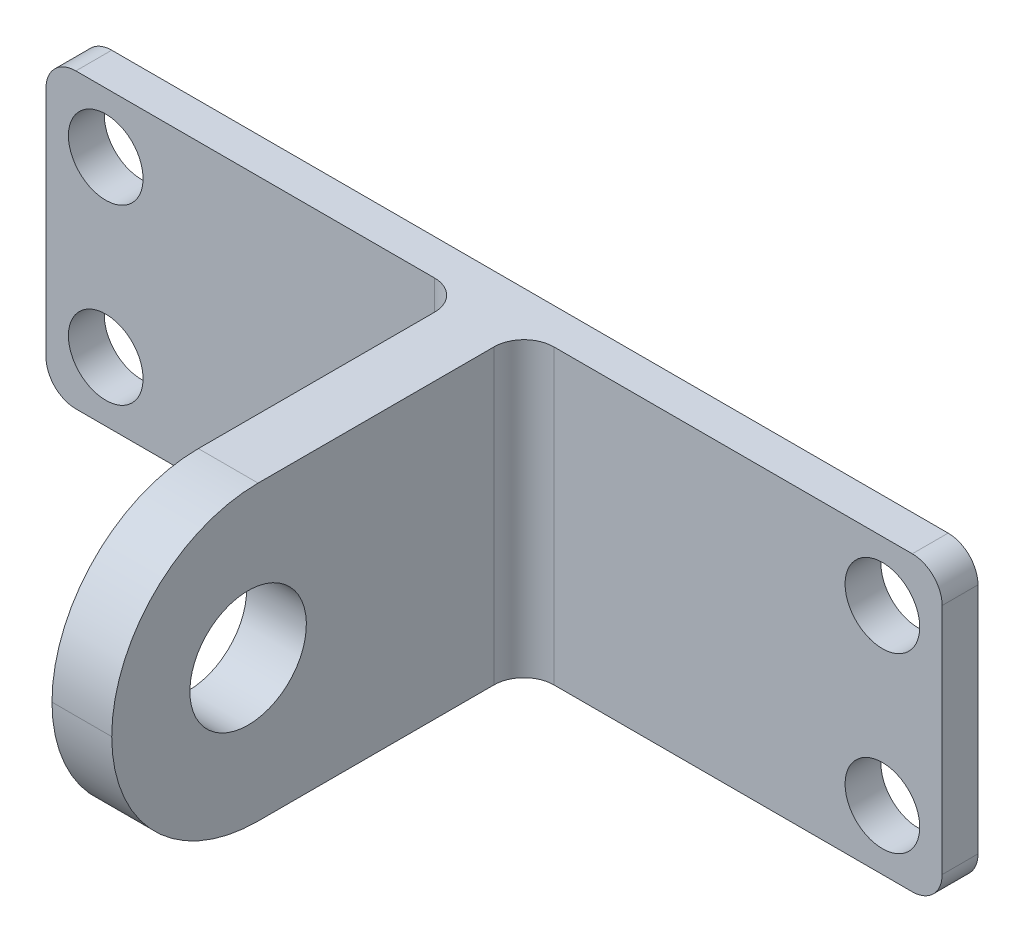
SolidWorks part; units mm, degrees
ref_plane "Front Plane" through (0, 0, 0) normal (0, 0, 1) x (1, 0, 0)
ref_plane "Top Plane" through (0, 0, 0) normal (0, 1, 0) x (1, 0, 0)
ref_plane "Right Plane" through (0, 0, 0) normal (1, 0, 0) x (0, 0, -1)
sketch "Sketch1" plane through (0, 0, 0) normal (0, 0, 1) x (1, 0, 0)
  line L0 (0, 27.7015) -> (0, 2.8095)
  line L1 (-33.02, 27.7015) -> (38.1, 27.7015)
  line L2 (-35.56, 25.1615) -> (-35.56, 5.3495)
  line L3 (-33.02, 2.8095) -> (38.1, 2.8095)
  line L4 (40.64, 25.1615) -> (40.64, 5.3495)
  line L5 (5.08, 27.7015) -> (5.08, 2.8095)
  line L6 (0, 27.7015) -> (5.08, 27.7015)
  line L7 (0, 2.8095) -> (5.08, 2.8095)
  circle A0 centre (-30.48, 22.6215) radius 3.175
  circle A1 centre (-30.48, 7.8895) radius 3.175
  circle A2 centre (35.56, 22.6215) radius 3.175
  circle A3 centre (35.56, 7.8895) radius 3.175
  arc A4 (-35.56, 25.1615) -> (-33.02, 27.7015) centre (-33.02, 25.1615) cw
  arc A5 (-33.02, 2.8095) -> (-35.56, 5.3495) centre (-33.02, 5.3495) cw
  arc A6 (40.64, 5.3495) -> (38.1, 2.8095) centre (38.1, 5.3495) cw
  arc A7 (38.1, 27.7015) -> (40.64, 25.1615) centre (38.1, 25.1615) cw
  point P10 (-35.56, 27.7015)
  point P17 (-35.56, 2.8095)
  point P20 (40.64, 2.8095)
  dimension "D1" = 5.08
  dimension "D3" = 76.2
  dimension "D11" = 2.54
  dimension "D12" = 2.54
  dimension "D13" = 2.54
  dimension "D14" = 2.54
  dimension "D2" = 5.08
  dimension "D4" = 24.892
  dimension "D5" = 5.08
  dimension "D6" = 5.08
  dimension "D7" = 5.08
  dimension "D8" = 5.08
  dimension "D9" = 5.08
  dimension "D10" = 5.08
  dimension "D15" = 35.56
  dimension "D16" = 35.56
extrude "Boss-Extrude9" add sketch "Sketch1" along normal blind 3.048 contours A5 L3 L0 L1 A4 L2 A1 A0 | A7 L1 L5 L3 A6 L4 A2 A3 region at (-16.7397, 15.2555, 0) region at (21.8197, 15.2555, 0)
extrude "Boss-Extrude10" add sketch "Sketch1<17>" along normal blind 38.1 contours L5 L1 L0 L3 region at (2.54, 15.2555, 0)
sketch "Sketch1<17>" plane through (0, 0, 0) normal (0, 0, 1) x (1, 0, 0) same geometry as "Sketch1"
fillet "Fillet3" radius 2.54 1 edges at (5.08, 15.2555, 3.048)
fillet "Fillet4" radius 2.54 1 edges at (0, 15.2555, 3.048)
fillet "Fillet6" radius 12.446 2 edges at (2.54, 2.8095, 38.1) (2.54, 27.7015, 38.1)
sketch "Sketch2" plane through (0, 0, 0) normal (-1, 0, 0) x (0, 0, 1)
  line L0 (25.654, 2.8095) -> (5.588, 2.8095) construction
  circle A0 centre (26.5017, 15.2555) radius 4.953
  point P2 (0, 0)
  point P4 (0, 0)
  dimension "D1" = 12.446
extrude "Cut-Extrude1" cut sketch "Sketch2" against normal blind 38.1 contours A0
